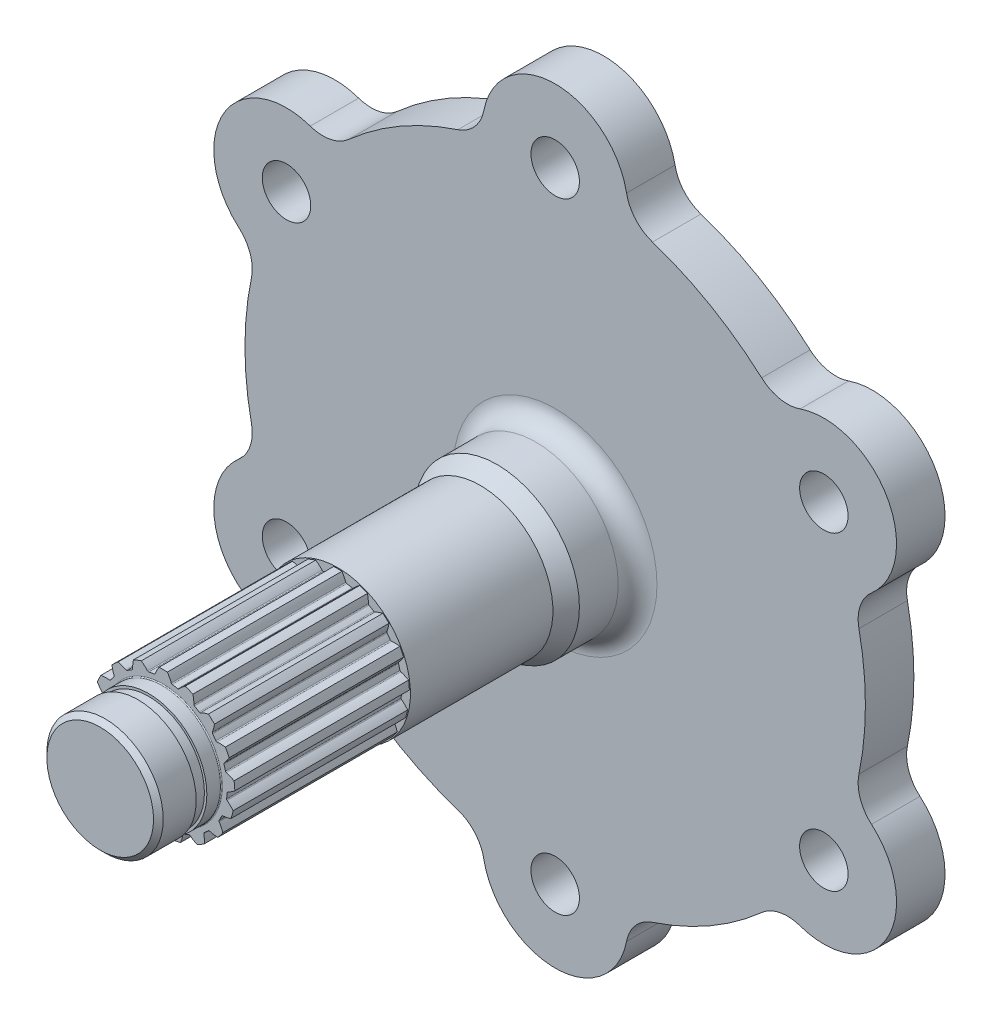
SolidWorks part; units mm, degrees
material "7075-O (SS)"
ref_plane "Front Plane" through (0, 0, 0) normal (0, 0, 1) x (1, 0, 0)
ref_plane "Top Plane" through (0, 0, 0) normal (0, 1, 0) x (1, 0, 0)
ref_plane "Right Plane" through (0, 0, 0) normal (1, 0, 0) x (0, 0, -1)
sketch "Sketch1" plane through (0, 0, 0) normal (0, 0, 1) x (1, 0, 0)
  line L0 (0, -55) -> (0, 55) construction
  line L1 (0, 39.5) -> (0, 0) construction
  line L2 (0, 0) -> (0, -39.5) construction
  circle A1 centre (0, 32) radius 2.5
  circle A2 centre (0, 0) radius 41.3
  circle A3 centre (27.7128, 16) radius 2.5
  circle A4 centre (0, 0) radius 41.3
  circle A5 centre (27.7128, -16) radius 2.5
  circle A6 centre (0, 0) radius 41.3
  circle A7 centre (0, -32) radius 2.5
  circle A8 centre (0, 0) radius 41.3
  circle A9 centre (-27.7128, -16) radius 2.5
  circle A10 centre (0, 0) radius 41.3
  circle A11 centre (-27.7128, 16) radius 2.5
  arc A12 (-7.4483, 31.1211) -> (-23.2275, 22.011) centre (0, 0) ccw
  arc A13 (7.4483, 31.1211) -> (-7.4483, 31.1211) centre (0, 32) ccw
  arc A14 (30.6758, 9.1101) -> (23.2275, 22.011) centre (27.7128, 16) ccw
  arc A15 (23.2275, -22.011) -> (30.6758, -9.1101) centre (27.7128, -16) ccw
  arc A16 (-7.4483, -31.1211) -> (7.4483, -31.1211) centre (0, -32) ccw
  arc A17 (-30.6758, -9.1101) -> (-23.2275, -22.011) centre (-27.7128, -16) ccw
  arc A18 (-23.2275, 22.011) -> (-30.6758, 9.1101) centre (-27.7128, 16) ccw
  circle A19 centre (0, 32) radius 7.5 construction
  arc A20 (-23.2275, -22.011) -> (-7.4483, -31.1211) centre (0, 0) ccw
  arc A21 (30.6758, -9.1101) -> (30.6758, 9.1101) centre (0, 0) ccw
  arc A22 (-30.6758, 9.1101) -> (-30.6758, -9.1101) centre (0, 0) ccw
  arc A23 (7.4483, -31.1211) -> (23.2275, -22.011) centre (0, 0) ccw
  arc A25 (23.2275, 22.011) -> (7.4483, 31.1211) centre (0, 0) ccw
  point P25 (0, 0)
  point P38 (0, 0)
  dimension "D1" = 32
  dimension "D5" = 5
  dimension "D6" = 64
  dimension "D3" = 5
  dimension "D2" = 6
  dimension "D4" = 6
extrude "Boss-Extrude1" add sketch "Sketch1" along normal blind 5 contours A11 A9 A7 A5 A3 A1 region at (0, 0, 0)
sketch "Sketch3" plane through (0, 0, 5) normal (0, 0, 1) x (1, 0, 0)
  circle A0 centre (0, 0) radius 7.5
  dimension "D1" = 15
extrude "Boss-Extrude2" add sketch "Sketch3" along normal blind 22.43
sketch "Sketch9" plane through (0, 0, 27.43) normal (0, 0, 1) x (1, 0, 0)
  arc A42 (3.0654, 6.727) -> (2.2666, 7.0365) centre (0, 0) ccw
  arc A43 (1.4878, 6.4262) -> (1.2121, 6.4839) centre (0, 0) ccw
  arc A44 (1.2121, 6.4839) -> (0.9342, 6.5297) centre (0, 0) ccw
  arc A45 (0.4284, 7.3801) -> (-0.4283, 7.3801) centre (0, 0) ccw
  arc A46 (-0.9341, 6.5297) -> (-1.212, 6.4839) centre (0, 0) ccw
  arc A47 (-1.212, 6.4839) -> (-1.4877, 6.4262) centre (0, 0) ccw
  arc A48 (-2.2665, 7.0365) -> (-3.0654, 6.727) centre (0, 0) ccw
  arc A49 (-3.2298, 5.7513) -> (-3.4724, 5.6082) centre (0, 0) ccw
  arc A50 (-3.4724, 5.6082) -> (-3.7087, 5.4549) centre (0, 0) ccw
  arc A51 (-4.6554, 5.7425) -> (-5.2885, 5.1654) centre (0, 0) ccw
  arc A52 (-5.0894, 4.1962) -> (-5.2639, 3.9751) centre (0, 0) ccw
  arc A53 (-5.2639, 3.9751) -> (-5.4288, 3.7468) centre (0, 0) ccw
  arc A54 (-6.4154, 3.6731) -> (-6.7973, 2.9062) centre (0, 0) ccw
  arc A55 (-6.2615, 2.0744) -> (-6.3444, 1.8052) centre (0, 0) ccw
  arc A56 (-6.3444, 1.8052) -> (-6.4156, 1.5327) centre (0, 0) ccw
  arc A57 (-7.3091, 1.1075) -> (-7.3881, 0.2544) centre (0, 0) ccw
  arc A58 (-6.588, -0.3276) -> (-6.568, -0.6086) centre (0, 0) ccw
  arc A59 (-6.568, -0.6086) -> (-6.5361, -0.8884) centre (0, 0) ccw
  arc A60 (-7.2156, -1.6076) -> (-6.9811, -2.4316) centre (0, 0) ccw
  arc A61 (-6.0248, -2.6854) -> (-5.9046, -2.9401) centre (0, 0) ccw
  arc A62 (-5.9046, -2.9401) -> (-5.7737, -3.1895) centre (0, 0) ccw
  arc A63 (-6.1476, -4.1056) -> (-5.6313, -4.7893) centre (0, 0) ccw
  arc A64 (-4.6479, -4.6805) -> (-4.4438, -4.8746) centre (0, 0) ccw
  arc A65 (-4.4438, -4.8746) -> (-4.2317, -5.0599) centre (0, 0) ccw
  arc A66 (-4.2493, -6.0491) -> (-3.5209, -6.5001) centre (0, 0) ccw
  arc A67 (-2.6432, -6.0434) -> (-2.3828, -6.1507) centre (0, 0) ccw
  arc A68 (-2.3828, -6.1507) -> (-2.1181, -6.2469) centre (0, 0) ccw
  arc A69 (-1.7771, -7.1757) -> (-0.935, -7.3331) centre (0, 0) ccw
  arc A70 (-0.2816, -6.5901) -> (0, -6.5962) centre (0, 0.0001) ccw
  arc A71 (0, -6.5962) -> (0.2816, -6.5901) centre (0, 0.0001) ccw
  arc A72 (0.935, -7.3331) -> (1.7772, -7.1757) centre (0, 0) ccw
  arc A73 (2.1181, -6.2469) -> (2.3828, -6.1507) centre (0, 0) ccw
  arc A74 (2.3828, -6.1507) -> (2.6432, -6.0434) centre (0, 0) ccw
  arc A75 (3.5209, -6.5001) -> (4.2493, -6.0491) centre (0, 0) ccw
  arc A76 (4.2317, -5.0599) -> (4.4438, -4.8746) centre (0, 0) ccw
  arc A77 (4.4438, -4.8746) -> (4.6479, -4.6805) centre (0, 0) ccw
  arc A78 (5.6313, -4.7893) -> (6.1476, -4.1056) centre (0, 0) ccw
  arc A79 (5.7738, -3.1895) -> (5.9047, -2.9401) centre (0, 0) ccw
  arc A80 (5.9047, -2.9401) -> (6.0248, -2.6854) centre (0, 0) ccw
  arc A81 (6.9811, -2.4316) -> (7.2156, -1.6076) centre (0, 0) ccw
  arc A82 (6.5361, -0.8884) -> (6.5681, -0.6086) centre (0, 0) ccw
  arc A83 (6.5681, -0.6086) -> (6.5881, -0.3276) centre (0, 0) ccw
  arc A84 (7.3881, 0.2544) -> (7.3091, 1.1075) centre (0, 0) ccw
  arc A85 (6.4157, 1.5327) -> (6.3444, 1.8052) centre (0, 0) ccw
  arc A86 (6.3444, 1.8052) -> (6.2615, 2.0744) centre (0, 0) ccw
  arc A87 (6.7973, 2.9062) -> (6.4155, 3.6731) centre (0, 0) ccw
  arc A88 (5.4288, 3.7468) -> (5.2639, 3.9751) centre (0, 0) ccw
  arc A89 (5.2639, 3.9751) -> (5.0894, 4.1962) centre (0, 0) ccw
  arc A90 (5.2885, 5.1654) -> (4.6554, 5.7425) centre (0, 0) ccw
  arc A91 (3.7087, 5.4549) -> (3.4725, 5.6082) centre (0, 0) ccw
  arc A92 (3.4725, 5.6082) -> (3.2299, 5.7513) centre (0, 0) ccw
  spline S0 degree 3 poles (3.2299, 5.7513) (3.2097, 5.7626) (3.1758, 5.7963) (3.1637, 5.8426) (3.1639, 5.8657) knots 0 0 0 0 0.499566 1 1 1 1
  spline S1 degree 6 poles (3.1639, 5.8657) (3.1648, 5.9848) (3.1603, 6.1142) (3.1493, 6.2536) (3.1305, 6.4026) (3.1029, 6.5607) (3.0654, 6.727) knots 0 0 0 0 0 0 0 1 1 1 1 1 1 1
  spline S2 degree 6 poles (2.2666, 7.0365) (2.1268, 6.9388) (2, 6.8406) (1.8857, 6.7431) (1.7836, 6.6475) (1.6931, 6.5549) (1.6136, 6.4663) knots 0 0 0 0 0 0 0 1 1 1 1 1 1 1
  spline S3 degree 3 poles (1.6136, 6.4663) (1.5982, 6.4491) (1.558, 6.423) (1.5102, 6.421) (1.4878, 6.4262) knots 0 0 0 0 0.500434 1 1 1 1
  spline S4 degree 3 poles (0.9342, 6.5297) (0.9113, 6.5329) (0.8675, 6.5521) (0.8395, 6.5909) (0.8313, 6.6126) knots 0 0 0 0 0.499566 1 1 1 1
  spline S5 degree 6 poles (0.8313, 6.6126) (0.7891, 6.7239) (0.7382, 6.8429) (0.6775, 6.969) (0.6062, 7.1011) (0.5234, 7.2385) (0.4284, 7.3801) knots 0 0 0 0 0 0 0 1 1 1 1 1 1 1
  spline S6 degree 6 poles (-0.4283, 7.3801) (-0.5234, 7.2385) (-0.6062, 7.1011) (-0.6775, 6.969) (-0.7382, 6.8429) (-0.7891, 6.7239) (-0.8313, 6.6126) knots 0 0 0 0 0 0 0 1 1 1 1 1 1 1
  spline S7 degree 3 poles (-0.8313, 6.6126) (-0.8394, 6.5909) (-0.8674, 6.5521) (-0.9113, 6.5329) (-0.9341, 6.5297) knots 0 0 0 0 0.500434 1 1 1 1
  spline S8 degree 3 poles (-1.4877, 6.4262) (-1.5102, 6.421) (-1.558, 6.423) (-1.5981, 6.4491) (-1.6135, 6.4663) knots 0 0 0 0 0.499566 1 1 1 1
  spline S9 degree 6 poles (-1.6135, 6.4663) (-1.6931, 6.5549) (-1.7836, 6.6475) (-1.8857, 6.7431) (-1.9999, 6.8406) (-2.1268, 6.9388) (-2.2665, 7.0365) knots 0 0 0 0 0 0 0 1 1 1 1 1 1 1
  spline S10 degree 6 poles (-3.0654, 6.727) (-3.1029, 6.5607) (-3.1305, 6.4026) (-3.1492, 6.2536) (-3.1603, 6.1142) (-3.1648, 5.9848) (-3.1639, 5.8657) knots 0 0 0 0 0 0 0 1 1 1 1 1 1 1
  spline S11 degree 3 poles (-3.1639, 5.8657) (-3.1637, 5.8426) (-3.1757, 5.7963) (-3.2097, 5.7626) (-3.2298, 5.7513) knots 0 0 0 0 0.500434 1 1 1 1
  spline S12 degree 3 poles (-3.7087, 5.4549) (-3.7277, 5.4418) (-3.7731, 5.4265) (-3.8199, 5.4363) (-3.8405, 5.4468) knots 0 0 0 0 0.499566 1 1 1 1
  spline S13 degree 6 poles (-3.8405, 5.4468) (-3.9467, 5.5007) (-4.0645, 5.5543) (-4.1942, 5.6066) (-4.336, 5.6562) (-4.4897, 5.7019) (-4.6554, 5.7425) knots 0 0 0 0 0 0 0 1 1 1 1 1 1 1
  spline S14 degree 6 poles (-5.2885, 5.1654) (-5.2633, 4.9967) (-5.232, 4.8394) (-5.1956, 4.6937) (-5.1556, 4.5597) (-5.113, 4.4374) (-5.0692, 4.3267) knots 0 0 0 0 0 0 0 1 1 1 1 1 1 1
  spline S15 degree 3 poles (-5.0692, 4.3267) (-5.0606, 4.3052) (-5.0552, 4.2577) (-5.0746, 4.214) (-5.0894, 4.1962) knots 0 0 0 0 0.500434 1 1 1 1
  spline S16 degree 3 poles (-5.4288, 3.7468) (-5.4418, 3.7278) (-5.4785, 3.6971) (-5.5257, 3.6893) (-5.5487, 3.6917) knots 0 0 0 0 0.499566 1 1 1 1
  spline S17 degree 6 poles (-5.5487, 3.6917) (-5.6672, 3.7035) (-5.7965, 3.711) (-5.9363, 3.7128) (-6.0864, 3.7079) (-6.2463, 3.695) (-6.4154, 3.6731) knots 0 0 0 0 0 0 0 1 1 1 1 1 1 1
  spline S18 degree 6 poles (-6.7973, 2.9062) (-6.7129, 2.758) (-6.6268, 2.6226) (-6.5403, 2.4998) (-6.4546, 2.3894) (-6.3707, 2.2907) (-6.2898, 2.2033) knots 0 0 0 0 0 0 0 1 1 1 1 1 1 1
  spline S19 degree 3 poles (-6.2898, 2.2033) (-6.2741, 2.1864) (-6.2518, 2.144) (-6.2542, 2.0962) (-6.2615, 2.0744) knots 0 0 0 0 0.500434 1 1 1 1
  spline S20 degree 3 poles (-6.4156, 1.5327) (-6.421, 1.5102) (-6.4441, 1.4683) (-6.4853, 1.444) (-6.5076, 1.4379) knots 0 0 0 0 0.499566 1 1 1 1
  spline S21 degree 6 poles (-6.5076, 1.4379) (-6.6224, 1.4062) (-6.7456, 1.3665) (-6.8767, 1.3177) (-7.0149, 1.2588) (-7.1593, 1.1891) (-7.3091, 1.1075) knots 0 0 0 0 0 0 0 1 1 1 1 1 1 1
  spline S22 degree 6 poles (-7.3881, 0.2544) (-7.2559, 0.1468) (-7.1267, 0.0516) (-7.0017, -0.0316) (-6.8818, -0.1036) (-6.768, -0.1653) (-6.661, -0.2176) knots 0 0 0 0 0 0 0 1 1 1 1 1 1 1
  spline S23 degree 3 poles (-6.661, -0.2176) (-6.6402, -0.2277) (-6.6042, -0.2592) (-6.5891, -0.3046) (-6.588, -0.3276) knots 0 0 0 0 0.500434 1 1 1 1
  spline S24 degree 3 poles (-6.5361, -0.8884) (-6.5329, -0.9113) (-6.5394, -0.9587) (-6.569, -0.9963) (-6.5876, -1.01) knots 0 0 0 0 0.499566 1 1 1 1
  spline S25 degree 6 poles (-6.5876, -1.01) (-6.6831, -1.081) (-6.7837, -1.1626) (-6.8883, -1.2555) (-6.9959, -1.3602) (-7.1054, -1.4775) (-7.2156, -1.6076) knots 0 0 0 0 0 0 0 1 1 1 1 1 1 1
  spline S26 degree 6 poles (-6.9811, -2.4316) (-6.8189, -2.4843) (-6.6641, -2.5263) (-6.5175, -2.5588) (-6.3797, -2.5826) (-6.2512, -2.5991) (-6.1326, -2.6092) knots 0 0 0 0 0 0 0 1 1 1 1 1 1 1
  spline S27 degree 3 poles (-6.1326, -2.6092) (-6.1096, -2.6111) (-6.0646, -2.6274) (-6.0341, -2.6643) (-6.0248, -2.6854) knots 0 0 0 0 0.500434 1 1 1 1
  spline S28 degree 3 poles (-5.7737, -3.1895) (-5.7625, -3.2097) (-5.7514, -3.2563) (-5.7655, -3.302) (-5.7779, -3.3215) knots 0 0 0 0 0.499566 1 1 1 1
  spline S29 degree 6 poles (-5.7779, -3.3215) (-5.8413, -3.4223) (-5.9056, -3.5347) (-5.9696, -3.659) (-6.0321, -3.7956) (-6.0918, -3.9445) (-6.1476, -4.1056) knots 0 0 0 0 0 0 0 1 1 1 1 1 1 1
  spline S30 degree 6 poles (-5.6313, -4.7893) (-5.461, -4.7798) (-5.3015, -4.7631) (-5.153, -4.7404) (-5.0159, -4.7128) (-4.8902, -4.6818) (-4.7759, -4.6483) knots 0 0 0 0 0 0 0 1 1 1 1 1 1 1
  spline S31 degree 3 poles (-4.7759, -4.6483) (-4.7538, -4.6418) (-4.7059, -4.6407) (-4.6642, -4.6642) (-4.6479, -4.6805) knots 0 0 0 0 0.500434 1 1 1 1
  spline S32 degree 3 poles (-4.2317, -5.0599) (-4.2139, -5.0746) (-4.1867, -5.114) (-4.1834, -5.1618) (-4.1878, -5.1844) knots 0 0 0 0 0.499566 1 1 1 1
  spline S33 degree 6 poles (-4.1878, -5.1844) (-4.2106, -5.3013) (-4.2299, -5.4293) (-4.2447, -5.5684) (-4.2536, -5.7183) (-4.2556, -5.8787) (-4.2493, -6.0491) knots 0 0 0 0 0 0 0 1 1 1 1 1 1 1
  spline S34 degree 6 poles (-3.5209, -6.5001) (-3.3656, -6.4298) (-3.2228, -6.3566) (-3.0926, -6.2818) (-2.9747, -6.2066) (-2.8687, -6.1322) (-2.7742, -6.0597) knots 0 0 0 0 0 0 0 1 1 1 1 1 1 1
  spline S35 degree 3 poles (-2.7742, -6.0597) (-2.7559, -6.0456) (-2.7117, -6.0273) (-2.6643, -6.0341) (-2.6432, -6.0434) knots 0 0 0 0 0.500434 1 1 1 1
  spline S36 degree 3 poles (-2.1181, -6.2469) (-2.0962, -6.2542) (-2.0566, -6.2811) (-2.0362, -6.3244) (-2.0322, -6.3472) knots 0 0 0 0 0.499566 1 1 1 1
  spline S37 degree 6 poles (-2.0322, -6.3472) (-2.0112, -6.4644) (-1.983, -6.5907) (-1.9465, -6.7258) (-1.9007, -6.8688) (-1.8445, -7.0191) (-1.7771, -7.1757) knots 0 0 0 0 0 0 0 1 1 1 1 1 1 1
  spline S38 degree 6 poles (-0.935, -7.3331) (-0.8156, -7.2114) (-0.7089, -7.0916) (-0.6145, -6.9747) (-0.5317, -6.862) (-0.4598, -6.7544) (-0.3979, -6.6527) knots 0 0 0 0 0 0 0 1 1 1 1 1 1 1
  spline S39 degree 3 poles (-0.3979, -6.6527) (-0.3859, -6.6329) (-0.3513, -6.5999) (-0.3046, -6.5891) (-0.2816, -6.5901) knots 0 0 0 0 0.500434 1 1 1 1
  spline S40 degree 3 poles (0.2816, -6.5901) (0.3047, -6.5891) (0.3513, -6.5999) (0.3859, -6.6329) (0.3979, -6.6527) knots 0 0 0 0 0.499566 1 1 1 1
  spline S41 degree 6 poles (0.3979, -6.6527) (0.4598, -6.7544) (0.5318, -6.862) (0.6146, -6.9747) (0.709, -7.0916) (0.8156, -7.2114) (0.935, -7.3331) knots 0 0 0 0 0 0 0 1 1 1 1 1 1 1
  spline S42 degree 6 poles (1.7772, -7.1757) (1.8446, -7.0191) (1.9007, -6.8688) (1.9465, -6.7258) (1.983, -6.5907) (2.0112, -6.4644) (2.0322, -6.3472) knots 0 0 0 0 0 0 0 1 1 1 1 1 1 1
  spline S43 degree 3 poles (2.0322, -6.3472) (2.0362, -6.3244) (2.0566, -6.2811) (2.0962, -6.2542) (2.1181, -6.2469) knots 0 0 0 0 0.500434 1 1 1 1
  spline S44 degree 3 poles (2.6432, -6.0434) (2.6644, -6.0341) (2.7117, -6.0273) (2.756, -6.0456) (2.7743, -6.0597) knots 0 0 0 0 0.499566 1 1 1 1
  spline S45 degree 6 poles (2.7743, -6.0597) (2.8687, -6.1322) (2.9747, -6.2066) (3.0926, -6.2818) (3.2229, -6.3566) (3.3656, -6.4298) (3.5209, -6.5001) knots 0 0 0 0 0 0 0 1 1 1 1 1 1 1
  spline S46 degree 6 poles (4.2493, -6.0491) (4.2556, -5.8787) (4.2537, -5.7183) (4.2447, -5.5684) (4.23, -5.4293) (4.2106, -5.3013) (4.1879, -5.1844) knots 0 0 0 0 0 0 0 1 1 1 1 1 1 1
  spline S47 degree 3 poles (4.1879, -5.1844) (4.1834, -5.1618) (4.1868, -5.114) (4.214, -5.0746) (4.2317, -5.0599) knots 0 0 0 0 0.500434 1 1 1 1
  spline S48 degree 3 poles (4.6479, -4.6805) (4.6642, -4.6642) (4.706, -4.6407) (4.7538, -4.6418) (4.7759, -4.6483) knots 0 0 0 0 0.499566 1 1 1 1
  spline S49 degree 6 poles (4.7759, -4.6483) (4.8902, -4.6818) (5.0159, -4.7128) (5.153, -4.7404) (5.3015, -4.7631) (5.461, -4.7798) (5.6313, -4.7893) knots 0 0 0 0 0 0 0 1 1 1 1 1 1 1
  spline S50 degree 6 poles (6.1476, -4.1056) (6.0919, -3.9445) (6.0321, -3.7956) (5.9696, -3.659) (5.9056, -3.5347) (5.8413, -3.4223) (5.7779, -3.3215) knots 0 0 0 0 0 0 0 1 1 1 1 1 1 1
  spline S51 degree 3 poles (5.7779, -3.3215) (5.7655, -3.302) (5.7515, -3.2563) (5.7626, -3.2097) (5.7738, -3.1895) knots 0 0 0 0 0.500434 1 1 1 1
  spline S52 degree 3 poles (6.0248, -2.6854) (6.0342, -2.6643) (6.0646, -2.6274) (6.1096, -2.6111) (6.1326, -2.6092) knots 0 0 0 0 0.499566 1 1 1 1
  spline S53 degree 6 poles (6.1326, -2.6092) (6.2513, -2.5991) (6.3797, -2.5826) (6.5175, -2.5588) (6.6641, -2.5263) (6.819, -2.4843) (6.9811, -2.4316) knots 0 0 0 0 0 0 0 1 1 1 1 1 1 1
  spline S54 degree 6 poles (7.2156, -1.6076) (7.1054, -1.4775) (6.9959, -1.3602) (6.8883, -1.2555) (6.7837, -1.1626) (6.6832, -1.081) (6.5876, -1.01) knots 0 0 0 0 0 0 0 1 1 1 1 1 1 1
  spline S55 degree 3 poles (6.5876, -1.01) (6.569, -0.9963) (6.5394, -0.9587) (6.5329, -0.9113) (6.5361, -0.8884) knots 0 0 0 0 0.500434 1 1 1 1
  spline S56 degree 3 poles (6.5881, -0.3276) (6.5892, -0.3046) (6.6042, -0.2592) (6.6403, -0.2277) (6.661, -0.2176) knots 0 0 0 0 0.499566 1 1 1 1
  spline S57 degree 6 poles (6.661, -0.2176) (6.768, -0.1653) (6.8819, -0.1036) (7.0017, -0.0316) (7.1268, 0.0516) (7.2559, 0.1468) (7.3881, 0.2544) knots 0 0 0 0 0 0 0 1 1 1 1 1 1 1
  spline S58 degree 6 poles (7.3091, 1.1075) (7.1593, 1.1891) (7.0149, 1.2588) (6.8767, 1.3177) (6.7456, 1.3665) (6.6224, 1.4062) (6.5076, 1.4379) knots 0 0 0 0 0 0 0 1 1 1 1 1 1 1
  spline S59 degree 3 poles (6.5076, 1.4379) (6.4853, 1.444) (6.4441, 1.4683) (6.421, 1.5102) (6.4157, 1.5327) knots 0 0 0 0 0.500434 1 1 1 1
  spline S60 degree 3 poles (6.2615, 2.0744) (6.2542, 2.0962) (6.2519, 2.144) (6.2741, 2.1864) (6.2899, 2.2033) knots 0 0 0 0 0.499566 1 1 1 1
  spline S61 degree 6 poles (6.2899, 2.2033) (6.3707, 2.2907) (6.4546, 2.3894) (6.5403, 2.4998) (6.6269, 2.6226) (6.7129, 2.758) (6.7973, 2.9062) knots 0 0 0 0 0 0 0 1 1 1 1 1 1 1
  spline S62 degree 6 poles (6.4155, 3.6731) (6.2464, 3.695) (6.0865, 3.7079) (5.9363, 3.7128) (5.7965, 3.711) (5.6672, 3.7035) (5.5488, 3.6917) knots 0 0 0 0 0 0 0 1 1 1 1 1 1 1
  spline S63 degree 3 poles (5.5488, 3.6917) (5.5258, 3.6893) (5.4786, 3.6971) (5.4418, 3.7278) (5.4288, 3.7468) knots 0 0 0 0 0.500434 1 1 1 1
  spline S64 degree 3 poles (5.0894, 4.1962) (5.0747, 4.214) (5.0552, 4.2577) (5.0606, 4.3052) (5.0692, 4.3267) knots 0 0 0 0 0.499566 1 1 1 1
  spline S65 degree 6 poles (5.0692, 4.3267) (5.113, 4.4374) (5.1556, 4.5597) (5.1957, 4.6937) (5.232, 4.8394) (5.2633, 4.9967) (5.2885, 5.1654) knots 0 0 0 0 0 0 0 1 1 1 1 1 1 1
  spline S66 degree 6 poles (4.6554, 5.7425) (4.4898, 5.7019) (4.336, 5.6562) (4.1943, 5.6066) (4.0645, 5.5543) (3.9467, 5.5007) (3.8405, 5.4468) knots 0 0 0 0 0 0 0 1 1 1 1 1 1 1
  spline S67 degree 3 poles (3.8405, 5.4468) (3.8199, 5.4363) (3.7731, 5.4265) (3.7278, 5.4418) (3.7087, 5.4549) knots 0 0 0 0 0.500434 1 1 1 1
extrude "Boss-Extrude7" add sketch "Sketch9" along normal blind 18
sketch "Sketch4" plane through (0, 0, 45.43) normal (0, 0, 1) x (1, 0, 0)
  circle A0 centre (0, 0) radius 6
  dimension "D2" = 12
extrude "Boss-Extrude3" add sketch "Sketch4" along normal blind 6.5
sketch "Sketch6" plane through (0, 0, 5) normal (0, 0, 1) x (1, 0, 0)
  circle A0 centre (0, 0) radius 8.5
  dimension "D1" = 17
extrude "Boss-Extrude5" add sketch "Sketch6" along normal blind 6
fillet "Fillet1" radius 2 1 edges at (8.5, 0, 5)
chamfer "Chamfer2" distance 1 angle 60 1 edges at (7.5, 0, 11) first distance on face at (7.5, 0, 11)
chamfer "Chamfer3" distance 0.5 angle 45 1 edges at (6, 0, 51.93)
fillet "Fillet2" radius 0.1 1 edges at (6, 0, 45.43)
fillet "Fillet3" radius 4 12 edges at (23.2275, -22.011, 2.5) (7.4483, -31.1211, 2.5) (-7.4483, -31.1211, 2.5) (-23.2275, -22.011, 2.5) (-30.6758, -9.1101, 2.5) (-30.6758, 9.1101, 2.5) (-23.2275, 22.011, 2.5) (-7.4483, 31.1211, 2.5) (7.4483, 31.1211, 2.5) (30.6758, -9.1101, 2.5) (30.6758, 9.1101, 2.5) (23.2275, 22.011, 2.5)
sketch "Sketch12" plane through (0, 0, 0) normal (1, 0, 0) x (0, 0, -1)
  line L0 (-46.93, 6) -> (-46.93, 5.75)
  line L1 (-46.93, 5.75) -> (-48.03, 5.75)
  line L2 (-48.03, 5.75) -> (-48.03, 6)
  line L4 (-45.53, 6) -> (-45.53, -6) construction
  line L5 (-51.93, 0) -> (-45.53, 0) construction
  line L6 (-51.93, 5.5) -> (-51.93, -5.5) construction
  line L7 (-46.93, 6) -> (-48.03, 6)
  dimension "D1" = 1.4
  dimension "D2" = 1.1
  dimension "D3" = 5.75
  dimension "D4" = 0.25
  dimension "D5" = 6
revolve "Cut-Revolve1" cut sketch "Sketch12" angle 360 about L5
sketch "Sketch13" plane through (0, 0, 0) normal (0, 0, -1) x (-1, 0, 0)
  circle A0 centre (0, 0) radius 24
  circle A1 centre (0, 0) radius 21
  dimension "D2" = 48
  dimension "D1" = 3
extrude "Boss-Extrude8" add sketch "Sketch13" along normal blind 4
chamfer "Chamfer4" distance 1 angle 45 2 edges at (-24, 0, -4) (-21, 0, 0)
fillet "Fillet4" [suppressed] radius 0.2
